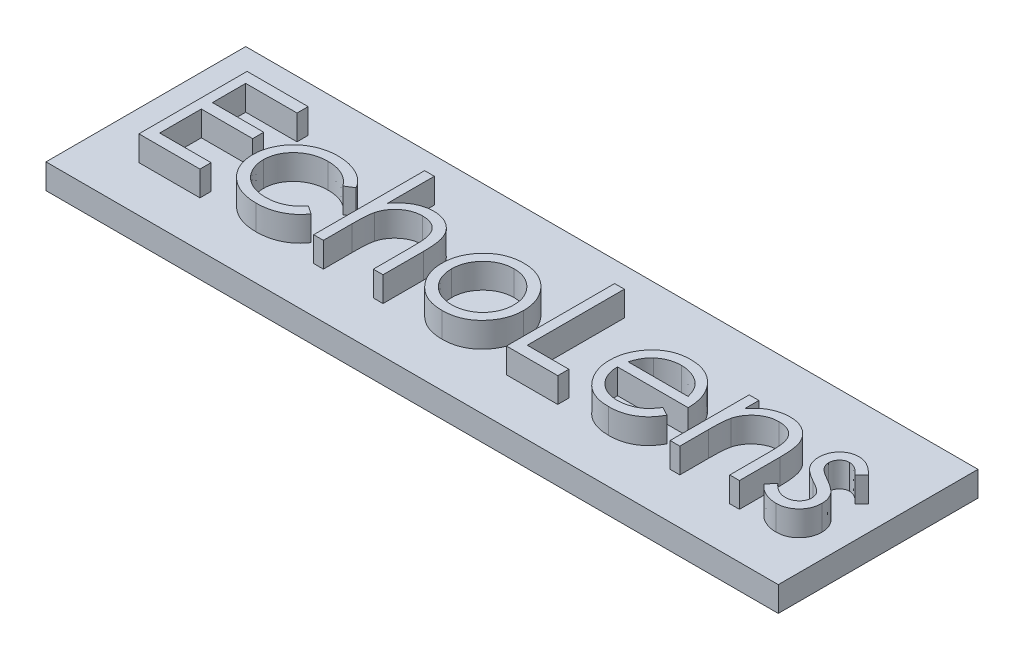
SolidWorks part; units mm, degrees
ref_plane "Front Plane" through (0, 0, 0) normal (0, 0, 1) x (1, 0, 0)
ref_plane "Top Plane" through (0, 0, 0) normal (0, 1, 0) x (1, 0, 0)
ref_plane "Right Plane" through (0, 0, 0) normal (1, 0, 0) x (0, 0, -1)
sketch "Sketch1" plane through (0, 0, 0) normal (0, 1, 0) x (1, 0, 0)
  line L0 (-20, 0) -> (20, 0) construction
  line L1 (-19.1667, 6.5) -> (-15.5, 6.5)
  line L2 (-15.5, 6.5) -> (-15.5, 5.8333)
  line L3 (-15.5, 5.8333) -> (-18.5833, 5.8333)
  line L4 (-18.5833, 5.8333) -> (-18.5833, 3.8333)
  line L5 (-18.5833, 3.8333) -> (-15.5, 3.8333)
  line L6 (-15.5, 3.8333) -> (-15.5, 3.1667)
  line L7 (-15.5, 3.1667) -> (-18.5833, 3.1667)
  line L8 (-18.5833, 3.1667) -> (-18.5833, 0.6667)
  line L9 (-18.5833, 0.6667) -> (-15.5, 0.6667)
  line L10 (-15.5, 0.6667) -> (-15.5, 0)
  line L11 (-15.5, 0) -> (-19.1667, 0)
  line L12 (-19.1667, 0) -> (-19.1667, 6.5)
  line L13 (-9.8333, 3.7201) -> (-10.3216, 3.4167)
  line L14 (-10.3216, 1.3333) -> (-9.8333, 1.013)
  line L15 (-8.6667, 6.6667) -> (-8.0833, 6.6667)
  line L16 (-8.0833, 6.6667) -> (-8.0833, 3.8529)
  line L17 (-4.5, 2.4258) -> (-4.5, 0)
  line L18 (-4.5, 0) -> (-5.0833, 0)
  line L19 (-5.0833, 0) -> (-5.0833, 2.2344)
  line L20 (-8.0833, 1.7174) -> (-8.0833, 0)
  line L21 (-8.0833, 0) -> (-8.6667, 0)
  line L22 (-8.6667, 0) -> (-8.6667, 6.6667)
  line L23 (2.9167, 6.5) -> (3.5, 6.5)
  line L24 (3.5, 6.5) -> (3.5, 0.6667)
  line L25 (3.5, 0.6667) -> (6, 0.6667)
  line L26 (6, 0.6667) -> (6, 0)
  line L27 (6, 0) -> (2.9167, 0)
  line L28 (2.9167, 0) -> (2.9167, 6.5)
  line L29 (10.8151, 1.5) -> (11.3333, 1.2279)
  line L30 (11.5833, 2.25) -> (7.3333, 2.25)
  line L31 (7.3945, 2.8333) -> (11, 2.8333)
  line L32 (12.75, 4.75) -> (13.3333, 4.75)
  line L33 (13.3333, 4.75) -> (13.3333, 3.8932)
  line L34 (16.9167, 2.4258) -> (16.9167, 0)
  line L35 (16.9167, 0) -> (16.3333, 0)
  line L36 (16.3333, 0) -> (16.3333, 2.2344)
  line L37 (13.3333, 1.7174) -> (13.3333, 0)
  line L38 (13.3333, 0) -> (12.75, 0)
  line L39 (12.75, 0) -> (12.75, 4.75)
  line L40 (20.5, 4.1576) -> (20.1042, 3.75)
  line L41 (17.8333, 0.5599) -> (18.2201, 1)
  line L43 (-22, 9.25) -> (22, 9.25)
  line L44 (-22, 9.25) -> (-22, -2.75)
  line L45 (-22, -2.75) -> (22, -2.75)
  line L46 (22, 9.25) -> (22, -2.75)
  spline S0 degree 3 poles (-10.3216, 3.4167) (-10.4224, 3.5511) (-10.5946, 3.7325) (-10.8586, 3.9283) (-11.0689, 4.0467) (-11.2944, 4.138) (-11.6201, 4.2264) (-11.877, 4.2503) (-12.0508, 4.25) knots 0 0 0 0 0.252584 0.373506 0.493364 0.614609 0.73847 1 1 1 1
  spline S1 degree 3 poles (-12.0508, 4.25) (-12.1908, 4.248) (-12.3987, 4.2357) (-12.6645, 4.1761) (-12.8521, 4.1183) (-13.0299, 4.0407) (-13.1982, 3.9464) (-13.3587, 3.8367) (-13.5065, 3.7096) (-13.6418, 3.5715) (-13.759, 3.4234) (-13.861, 3.2697) (-13.9411, 3.1068) (-14.0065, 2.9382) (-14.065, 2.699) (-14.084, 2.5135) (-14.0833, 2.388) knots 0 0 0 0 0.136921 0.201969 0.265462 0.328248 0.390817 0.45355 0.517542 0.580738 0.641922 0.701597 0.760313 0.818757 0.877718 1 1 1 1
  spline S2 degree 3 poles (-14.0833, 2.388) (-14.0829, 2.223) (-14.0506, 1.9744) (-13.9377, 1.6602) (-13.8226, 1.4342) (-13.6768, 1.2251) (-13.5056, 1.0376) (-13.3089, 0.8753) (-13.0884, 0.7406) (-12.8493, 0.6325) (-12.504, 0.5277) (-12.2309, 0.5007) (-12.0469, 0.5) knots 0 0 0 0 0.159965 0.240321 0.322529 0.405024 0.486597 0.567865 0.651333 0.736238 0.821529 1 1 1 1
  spline S3 degree 3 poles (-12.0469, 0.5) (-11.8779, 0.5001) (-11.6274, 0.5237) (-11.3088, 0.6127) (-11.0852, 0.7038) (-10.874, 0.8219) (-10.6058, 1.0188) (-10.4279, 1.1994) (-10.3216, 1.3333) knots 0 0 0 0 0.255447 0.377298 0.498442 0.619372 0.741857 1 1 1 1
  spline S4 degree 3 poles (-9.8333, 1.013) (-9.8897, 0.9272) (-9.9815, 0.8035) (-10.121, 0.6539) (-10.2323, 0.5497) (-10.3495, 0.4508) (-10.4764, 0.3619) (-10.6089, 0.2781) (-10.7487, 0.2027) (-10.8942, 0.1349) (-11.0453, 0.0766) (-11.2012, 0.0265) (-11.3623, -0.0133) (-11.5287, -0.0451) (-11.76, -0.0738) (-11.9367, -0.0852) (-12.056, -0.0833) knots 0 0 0 0 0.119069 0.178197 0.236957 0.295932 0.355856 0.416473 0.477742 0.539903 0.602538 0.665422 0.729765 0.794829 0.861827 1 1 1 1
  spline S5 degree 3 poles (-12.056, -0.0833) (-12.2366, -0.0852) (-12.5029, -0.0624) (-12.8456, 0.0111) (-13.0864, 0.0882) (-13.3154, 0.1876) (-13.5325, 0.3089) (-13.7368, 0.4533) (-13.9265, 0.6182) (-14.1006, 0.7969) (-14.2502, 0.9898) (-14.3799, 1.1897) (-14.4841, 1.4011) (-14.5669, 1.6211) (-14.6438, 1.9318) (-14.6672, 2.173) (-14.6667, 2.3359) knots 0 0 0 0 0.136335 0.201096 0.26445 0.327005 0.389391 0.451976 0.51567 0.578973 0.640167 0.69974 0.758685 0.81782 0.876984 1 1 1 1
  spline S6 degree 3 poles (-14.6667, 2.3359) (-14.6683, 2.4476) (-14.654, 2.6135) (-14.6213, 2.8322) (-14.5805, 2.9912) (-14.5332, 3.1483) (-14.4729, 3.3017) (-14.4022, 3.452) (-14.3219, 3.5989) (-14.2314, 3.7399) (-14.1314, 3.8732) (-14.0254, 4.0003) (-13.9087, 4.1167) (-13.786, 4.2273) (-13.654, 4.329) (-13.5134, 4.4221) (-13.3664, 4.5084) (-13.2129, 4.5852) (-13.054, 4.6514) (-12.8906, 4.7079) (-12.7224, 4.7527) (-12.5506, 4.7902) (-12.3122, 4.8223) (-12.1306, 4.834) (-12.0078, 4.8333) knots 0 0 0 0 0.082136 0.122636 0.162831 0.203007 0.243526 0.284173 0.32541 0.366855 0.407551 0.448187 0.488683 0.529015 0.569843 0.61137 0.653238 0.695446 0.737751 0.780043 0.822807 0.865978 0.909595 1 1 1 1
  spline S7 degree 3 poles (-12.0078, 4.8333) (-11.8526, 4.8338) (-11.6211, 4.8144) (-11.3179, 4.7561) (-11.0985, 4.6919) (-10.8891, 4.6142) (-10.6931, 4.5269) (-10.5151, 4.4255) (-10.3518, 4.3146) (-10.203, 4.1894) (-10.019, 3.9996) (-9.9014, 3.8368) (-9.8333, 3.7201) knots 0 0 0 0 0.182081 0.27191 0.362049 0.450066 0.533976 0.613602 0.690198 0.765413 0.841437 1 1 1 1
  spline S8 degree 3 poles (-8.0833, 3.8529) (-7.966, 4.0089) (-7.7716, 4.2191) (-7.4828, 4.4546) (-7.2593, 4.5919) (-7.0271, 4.7002) (-6.7025, 4.8039) (-6.4468, 4.833) (-6.276, 4.8333) knots 0 0 0 0 0.273996 0.400684 0.522555 0.641534 0.759969 1 1 1 1
  spline S9 degree 3 poles (-6.276, 4.8333) (-6.1045, 4.8322) (-5.8484, 4.8043) (-5.5317, 4.6878) (-5.315, 4.5706) (-5.1203, 4.4244) (-4.9479, 4.2558) (-4.8071, 4.0602) (-4.7112, 3.8796) (-4.6489, 3.7189) (-4.6094, 3.581) (-4.576, 3.4274) (-4.5468, 3.2581) (-4.5274, 3.0723) (-4.5056, 2.7934) (-4.4986, 2.5761) (-4.5, 2.4258) knots 0 0 0 0 0.151155 0.223454 0.295497 0.36692 0.436794 0.506696 0.577864 0.615912 0.658048 0.703776 0.75408 0.808979 0.867913 1 1 1 1
  spline S10 degree 3 poles (-5.0833, 2.2344) (-5.0842, 2.3581) (-5.0846, 2.5352) (-5.0916, 2.7605) (-5.0996, 2.9041) (-5.1082, 3.031) (-5.1224, 3.1665) (-5.1379, 3.2593) (-5.151, 3.3151) knots 0 0 0 0 0.342141 0.489871 0.623312 0.740056 0.841468 1 1 1 1
  spline S11 degree 3 poles (-5.151, 3.3151) (-5.1871, 3.4575) (-5.2624, 3.6607) (-5.4263, 3.8872) (-5.5708, 4.0208) (-5.739, 4.1255) (-6.0064, 4.2265) (-6.2273, 4.2507) (-6.3789, 4.25) knots 0 0 0 0 0.261954 0.379638 0.494379 0.609866 0.729887 1 1 1 1
  spline S12 degree 3 poles (-6.3789, 4.25) (-6.4717, 4.2504) (-6.6105, 4.2399) (-6.79, 4.2011) (-6.9207, 4.1623) (-7.0459, 4.1095) (-7.1691, 4.0483) (-7.2868, 3.9735) (-7.4012, 3.8895) (-7.5076, 3.7965) (-7.6066, 3.6983) (-7.6949, 3.5938) (-7.7749, 3.4846) (-7.8439, 3.3692) (-7.9247, 3.2082) (-7.9701, 3.08) (-7.9935, 2.9922) knots 0 0 0 0 0.126694 0.189084 0.250363 0.312516 0.374243 0.43785 0.502657 0.567745 0.630576 0.692772 0.754268 0.815121 0.876051 1 1 1 1
  spline S13 degree 3 poles (-7.9935, 2.9922) (-8.0109, 2.9236) (-8.0304, 2.8103) (-8.0495, 2.6461) (-8.0626, 2.4958) (-8.0707, 2.3269) (-8.0827, 2.0657) (-8.0825, 1.8602) (-8.0833, 1.7174) knots 0 0 0 0 0.165611 0.269045 0.387448 0.518827 0.665394 1 1 1 1
  spline S14 degree 3 poles (-0.8724, 4.8333) (-0.6977, 4.8351) (-0.4391, 4.8099) (-0.1083, 4.727) (0.1253, 4.6431) (0.3452, 4.5303) (0.6281, 4.3491) (0.8169, 4.1769) (0.9323, 4.0508) knots 0 0 0 0 0.258332 0.382134 0.503804 0.624693 0.746871 1 1 1 1
  spline S15 degree 3 poles (0.9323, 4.0508) (1.0382, 3.935) (1.1801, 3.7494) (1.3328, 3.4813) (1.424, 3.2729) (1.4958, 3.0568) (1.5648, 2.7542) (1.5825, 2.5197) (1.5833, 2.362) knots 0 0 0 0 0.253834 0.376506 0.498534 0.621368 0.744565 1 1 1 1
  spline S16 degree 3 poles (1.5833, 2.362) (1.5843, 2.2031) (1.5625, 1.967) (1.4908, 1.6617) (1.415, 1.4428) (1.3178, 1.2313) (1.1991, 1.0281) (1.0582, 0.8328) (0.8985, 0.6471) (0.722, 0.476) (0.5305, 0.3268) (0.3278, 0.199) (0.1111, 0.096) (-0.1174, 0.0149) (-0.4444, -0.0628) (-0.6998, -0.0827) (-0.8724, -0.0833) knots 0 0 0 0 0.123337 0.183265 0.243172 0.302898 0.363774 0.425605 0.489659 0.553785 0.616222 0.677854 0.739517 0.802097 0.865866 1 1 1 1
  spline S17 degree 3 poles (-0.8724, -0.0833) (-1.0459, -0.0825) (-1.3022, -0.0631) (-1.63, 0.0149) (-1.8589, 0.0963) (-2.0764, 0.199) (-2.2803, 0.3264) (-2.472, 0.476) (-2.6485, 0.6471) (-2.8082, 0.8328) (-2.9491, 1.0281) (-3.0678, 1.2313) (-3.165, 1.4428) (-3.2408, 1.6617) (-3.3125, 1.967) (-3.3343, 2.2031) (-3.3333, 2.362) knots 0 0 0 0 0.134635 0.198324 0.260825 0.322714 0.384555 0.446913 0.510958 0.574931 0.636685 0.697483 0.757134 0.816966 0.876818 1 1 1 1
  spline S18 degree 3 poles (-3.3333, 2.362) (-3.3324, 2.5193) (-3.3147, 2.7533) (-3.2459, 3.0551) (-3.1741, 3.2704) (-3.0821, 3.4779) (-2.9314, 3.7467) (-2.7871, 3.9308) (-2.6823, 4.0469) knots 0 0 0 0 0.255238 0.378679 0.501088 0.622714 0.746241 1 1 1 1
  spline S19 degree 3 poles (-2.6823, 4.0469) (-2.5679, 4.1747) (-2.3775, 4.3453) (-2.0952, 4.5301) (-1.8729, 4.6407) (-1.6395, 4.7275) (-1.3073, 4.8099) (-1.048, 4.8349) (-0.8724, 4.8333) knots 0 0 0 0 0.252713 0.374819 0.496436 0.617911 0.741288 1 1 1 1
  spline S20 degree 3 poles (-0.875, 4.25) (-0.9994, 4.2497) (-1.1843, 4.2329) (-1.4219, 4.1751) (-1.5917, 4.1146) (-1.7545, 4.0364) (-1.9103, 3.9404) (-2.0597, 3.8278) (-2.1997, 3.6988) (-2.3282, 3.5579) (-2.4405, 3.4077) (-2.536, 3.2508) (-2.6156, 3.0869) (-2.6748, 2.9144) (-2.7331, 2.6726) (-2.7497, 2.4846) (-2.75, 2.3581) knots 0 0 0 0 0.126044 0.187165 0.247399 0.30838 0.36978 0.432584 0.497641 0.562401 0.625557 0.687332 0.748313 0.809791 0.871768 1 1 1 1
  spline S21 degree 3 poles (-2.75, 2.3581) (-2.7496, 2.1934) (-2.7206, 1.9458) (-2.6123, 1.6338) (-2.5036, 1.4117) (-2.3672, 1.2062) (-2.2066, 1.0229) (-2.0234, 0.8647) (-1.8198, 0.7334) (-1.6, 0.6293) (-1.2873, 0.5292) (-1.0409, 0.4981) (-0.875, 0.5) knots 0 0 0 0 0.168179 0.251488 0.335841 0.419834 0.502345 0.583649 0.665931 0.748717 0.831047 1 1 1 1
  spline S22 degree 3 poles (-0.875, 0.5) (-0.7092, 0.4983) (-0.463, 0.5287) (-0.1509, 0.6296) (0.0686, 0.7333) (0.2721, 0.8652) (0.4566, 1.022) (0.6159, 1.2067) (0.7521, 1.412) (0.8625, 1.6335) (0.9704, 1.9459) (0.9997, 2.1933) (1, 2.3581) knots 0 0 0 0 0.168983 0.250908 0.333708 0.416005 0.49766 0.579893 0.663902 0.748466 0.831791 1 1 1 1
  spline S23 degree 3 poles (1, 2.3581) (0.9997, 2.4846) (0.9831, 2.6726) (0.9248, 2.9144) (0.8655, 3.0868) (0.7862, 3.2512) (0.6889, 3.4073) (0.577, 3.5584) (0.447, 3.6983) (0.3072, 3.8278) (0.1577, 3.9404) (0.0021, 4.036) (-0.1602, 4.1153) (-0.33, 4.1746) (-0.5669, 4.2333) (-0.7511, 4.2493) (-0.875, 4.25) knots 0 0 0 0 0.128274 0.19027 0.251768 0.312769 0.374793 0.43797 0.503047 0.568125 0.63095 0.692369 0.752973 0.813641 0.874355 1 1 1 1
  spline S24 degree 3 poles (11.3333, 1.2279) (11.2563, 1.0836) (11.1272, 0.8812) (10.9286, 0.6402) (10.7706, 0.4884) (10.6041, 0.356) (10.4282, 0.2403) (10.2419, 0.1416) (10.0453, 0.0585) (9.8368, -0.0053) (9.5352, -0.0672) (9.2996, -0.0833) (9.1393, -0.0833) knots 0 0 0 0 0.181661 0.265874 0.346355 0.4246 0.501903 0.579992 0.658443 0.738672 0.821894 1 1 1 1
  spline S25 degree 3 poles (9.1393, -0.0833) (8.9615, -0.0833) (8.6998, -0.0628) (8.3669, 0.0173) (8.1381, 0.0989) (7.925, 0.2055) (7.7272, 0.3355) (7.5437, 0.488) (7.3802, 0.6644) (7.233, 0.8533) (7.1032, 1.0501) (6.9946, 1.2543) (6.9063, 1.4646) (6.835, 1.6798) (6.768, 1.9778) (6.7517, 2.2078) (6.75, 2.362) knots 0 0 0 0 0.139629 0.204797 0.268135 0.329814 0.391301 0.453434 0.516552 0.579631 0.641119 0.701294 0.76081 0.819932 0.87892 1 1 1 1
  spline S26 degree 3 poles (6.75, 2.362) (6.7518, 2.5065) (6.7653, 2.7221) (6.824, 3.0017) (6.8837, 3.2039) (6.9609, 3.3999) (7.0875, 3.6553) (7.2086, 3.8337) (7.2969, 3.9479) knots 0 0 0 0 0.253768 0.377428 0.500551 0.623296 0.746578 1 1 1 1
  spline S27 degree 3 poles (7.2969, 3.9479) (7.4094, 4.0885) (7.5928, 4.2852) (7.88, 4.4909) (8.1058, 4.6172) (8.3479, 4.7131) (8.6943, 4.8106) (8.9689, 4.8311) (9.1536, 4.8333) knots 0 0 0 0 0.253589 0.374643 0.49534 0.616325 0.739759 1 1 1 1
  spline S28 degree 3 poles (9.1536, 4.8333) (9.3446, 4.8341) (9.6267, 4.8065) (9.9844, 4.7075) (10.233, 4.6052) (10.4664, 4.473) (10.7603, 4.2519) (10.9524, 4.0482) (11.0664, 3.8984) knots 0 0 0 0 0.259033 0.38188 0.502258 0.622752 0.744743 1 1 1 1
  spline S29 degree 3 poles (11.0664, 3.8984) (11.1516, 3.7891) (11.2629, 3.6115) (11.381, 3.3574) (11.4523, 3.1552) (11.5099, 2.9438) (11.5667, 2.6423) (11.5804, 2.4083) (11.5833, 2.25) knots 0 0 0 0 0.236255 0.356174 0.47725 0.60154 0.729618 1 1 1 1
  spline S30 degree 3 poles (7.3333, 2.25) (7.3367, 2.127) (7.3531, 1.9452) (7.4094, 1.7127) (7.4674, 1.551) (7.5377, 1.397) (7.6239, 1.2518) (7.7267, 1.1162) (7.8413, 0.9888) (7.9689, 0.8754) (8.1031, 0.7739) (8.2459, 0.6889) (8.3962, 0.6198) (8.5536, 0.5658) (8.7764, 0.5155) (8.9494, 0.4994) (9.0664, 0.5) knots 0 0 0 0 0.134476 0.198391 0.260753 0.321829 0.383037 0.444653 0.507398 0.569825 0.630778 0.690929 0.750945 0.811049 0.872331 1 1 1 1
  spline S31 degree 3 poles (9.0664, 0.5) (9.1819, 0.4994) (9.3552, 0.513) (9.5815, 0.5604) (9.7472, 0.6085) (9.9062, 0.6671) (10.0533, 0.7379) (10.1887, 0.8162) (10.3152, 0.9057) (10.4378, 1.0153) (10.6115, 1.21) (10.7361, 1.3764) (10.8151, 1.5) knots 0 0 0 0 0.163879 0.245659 0.327726 0.40861 0.485749 0.559169 0.630268 0.705306 0.792065 1 1 1 1
  spline S32 degree 3 poles (11, 2.8333) (10.9631, 2.9833) (10.8895, 3.1948) (10.7549, 3.4491) (10.6406, 3.6081) (10.5109, 3.7492) (10.3611, 3.8726) (10.1932, 3.9829) (10.0079, 4.0761) (9.8117, 4.1552) (9.5372, 4.2269) (9.3256, 4.2521) (9.1836, 4.25) knots 0 0 0 0 0.185231 0.267501 0.3444 0.419595 0.496891 0.576638 0.660268 0.745387 0.83004 1 1 1 1
  spline S33 degree 3 poles (9.1836, 4.25) (9.0686, 4.2503) (8.8977, 4.2378) (8.6779, 4.1901) (8.5206, 4.1419) (8.3709, 4.0776) (8.1758, 3.9765) (8.0442, 3.8758) (7.9596, 3.8047) knots 0 0 0 0 0.259141 0.384162 0.505992 0.629098 0.750669 1 1 1 1
  spline S34 degree 3 poles (7.9596, 3.8047) (7.8949, 3.7501) (7.8072, 3.6556) (7.7018, 3.5167) (7.6287, 3.3997) (7.5618, 3.2723) (7.4759, 3.0854) (7.4251, 2.9361) (7.3945, 2.8333) knots 0 0 0 0 0.22258 0.3385 0.458709 0.585535 0.717518 1 1 1 1
  spline S35 degree 3 poles (13.3333, 3.8932) (13.451, 4.0459) (13.6384, 4.2593) (13.9305, 4.4832) (14.1533, 4.6135) (14.3867, 4.7115) (14.7126, 4.8073) (14.9689, 4.8324) (15.1406, 4.8333) knots 0 0 0 0 0.273569 0.398988 0.51993 0.63811 0.756589 1 1 1 1
  spline S36 degree 3 poles (15.1406, 4.8333) (15.3122, 4.8322) (15.5682, 4.8043) (15.885, 4.6878) (16.1016, 4.5705) (16.2968, 4.4245) (16.4683, 4.2544) (16.6101, 4.0588) (16.7052, 3.8773) (16.7678, 3.7163) (16.8072, 3.5784) (16.8407, 3.4248) (16.8698, 3.2559) (16.8894, 3.0706) (16.911, 2.7925) (16.9181, 2.5756) (16.9167, 2.4258) knots 0 0 0 0 0.151178 0.223488 0.295543 0.366976 0.437131 0.507044 0.57856 0.616614 0.658756 0.704491 0.754803 0.809332 0.868274 1 1 1 1
  spline S37 degree 3 poles (16.3333, 2.2344) (16.3324, 2.3581) (16.3322, 2.5352) (16.3249, 2.7605) (16.3176, 2.9042) (16.3068, 3.0309) (16.2932, 3.1665) (16.2774, 3.2593) (16.2643, 3.3151) knots 0 0 0 0 0.34211 0.489826 0.623254 0.74008 0.841483 1 1 1 1
  spline S38 degree 3 poles (16.2643, 3.3151) (16.2318, 3.4577) (16.1581, 3.6613) (15.9942, 3.8871) (15.8496, 4.0212) (15.6802, 4.1254) (15.4119, 4.2261) (15.1907, 4.2509) (15.0391, 4.25) knots 0 0 0 0 0.260833 0.378476 0.493178 0.609281 0.729981 1 1 1 1
  spline S39 degree 3 poles (15.0391, 4.25) (14.9463, 4.2504) (14.8075, 4.2399) (14.628, 4.2011) (14.4972, 4.1624) (14.3718, 4.1091) (14.2478, 4.0487) (14.1299, 3.9734) (14.0155, 3.8895) (13.9091, 3.7965) (13.81, 3.6983) (13.7217, 3.5938) (13.6417, 3.4846) (13.5727, 3.3692) (13.4919, 3.2082) (13.4466, 3.08) (13.4232, 2.9922) knots 0 0 0 0 0.126627 0.188984 0.25023 0.312351 0.374574 0.438148 0.50292 0.567974 0.630771 0.692935 0.754398 0.815218 0.876117 1 1 1 1
  spline S40 degree 3 poles (13.4232, 2.9922) (13.4058, 2.9227) (13.3864, 2.8086) (13.3672, 2.6435) (13.354, 2.4932) (13.3461, 2.3247) (13.3339, 2.0644) (13.3342, 1.8598) (13.3333, 1.7174) knots 0 0 0 0 0.167615 0.271052 0.38946 0.520843 0.666399 1 1 1 1
  spline S41 degree 3 poles (20.1042, 3.75) (20.0395, 3.8271) (19.9402, 3.9347) (19.7957, 4.0536) (19.6935, 4.126) (19.5905, 4.1806) (19.4566, 4.233) (19.3522, 4.2499) (19.2839, 4.25) knots 0 0 0 0 0.305036 0.441309 0.565963 0.683525 0.793334 1 1 1 1
  spline S42 degree 3 poles (19.2839, 4.25) (19.2028, 4.2517) (19.0819, 4.2255) (18.9383, 4.1446) (18.8451, 4.0593) (18.7663, 3.9613) (18.6889, 3.8149) (18.6669, 3.6923) (18.6667, 3.6107) knots 0 0 0 0 0.245901 0.369166 0.498511 0.628504 0.751028 1 1 1 1
  spline S43 degree 3 poles (18.6667, 3.6107) (18.6668, 3.5357) (18.6959, 3.3794) (18.7786, 3.2438) (18.8281, 3.1797) knots 0 0 0 0 0.479403 1 1 1 1
  spline S44 degree 3 poles (18.8281, 3.1797) (18.8578, 3.1394) (18.9158, 3.0845) (19.0004, 3.0099) (19.0808, 2.9505) (19.1714, 2.8881) (19.3141, 2.8) (19.4259, 2.7321) (19.5065, 2.6901) knots 0 0 0 0 0.17756 0.283982 0.402217 0.533568 0.676121 1 1 1 1
  spline S45 degree 3 poles (19.5065, 2.6901) (19.6044, 2.636) (19.7453, 2.5545) (19.9193, 2.4378) (20.0334, 2.3549) (20.1336, 2.271) (20.2481, 2.1666) (20.3208, 2.0816) (20.362, 2.0234) knots 0 0 0 0 0.307115 0.446213 0.574876 0.694152 0.804581 1 1 1 1
  spline S46 degree 3 poles (20.362, 2.0234) (20.4327, 1.9166) (20.5517, 1.6814) (20.5815, 1.4195) (20.5833, 1.2891) knots 0 0 0 0 0.495235 1 1 1 1
  spline S47 degree 3 poles (20.5833, 1.2891) (20.5825, 1.1967) (20.5722, 1.0591) (20.5295, 0.8832) (20.4867, 0.7575) (20.4288, 0.6387) (20.3609, 0.5239) (20.2794, 0.4155) (20.1864, 0.3136) (20.0845, 0.2206) (19.9759, 0.1388) (19.8603, 0.0709) (19.7386, 0.0147) (19.6105, -0.03) (19.4285, -0.072) (19.2868, -0.0827) (19.1914, -0.0833) knots 0 0 0 0 0.127199 0.188597 0.24864 0.309525 0.370037 0.431889 0.495704 0.559519 0.621372 0.682397 0.743568 0.805498 0.86864 1 1 1 1
  spline S48 degree 3 poles (19.1914, -0.0833) (19.0609, -0.0843) (18.8656, -0.0618) (18.6138, 0.0101) (18.4311, 0.0837) (18.2583, 0.177) (18.048, 0.3248) (17.9118, 0.4604) (17.8333, 0.5599) knots 0 0 0 0 0.251724 0.377219 0.504694 0.631458 0.755401 1 1 1 1
  spline S49 degree 3 poles (18.2201, 1) (18.29, 0.9222) (18.3982, 0.8132) (18.5577, 0.6953) (18.6743, 0.6235) (18.7936, 0.5683) (18.9542, 0.5164) (19.0789, 0.4996) (19.1615, 0.5) knots 0 0 0 0 0.285904 0.417172 0.540501 0.659238 0.775006 1 1 1 1
  spline S50 degree 3 poles (19.1615, 0.5) (19.2714, 0.499) (19.4345, 0.5274) (19.6308, 0.6236) (19.7572, 0.7239) (19.8646, 0.8409) (19.9688, 1.016) (20.0006, 1.1655) (20, 1.2643) knots 0 0 0 0 0.261896 0.387836 0.517686 0.644509 0.764718 1 1 1 1
  spline S51 degree 3 poles (20, 1.2643) (19.9997, 1.346) (19.9737, 1.5099) (19.8916, 1.6544) (19.8398, 1.7174) knots 0 0 0 0 0.500453 1 1 1 1
  spline S52 degree 3 poles (19.8398, 1.7174) (19.8086, 1.7551) (19.7506, 1.8097) (19.6616, 1.8804) (19.5779, 1.9405) (19.4813, 2.0029) (19.3278, 2.0932) (19.2059, 2.1616) (19.1198, 2.207) knots 0 0 0 0 0.167462 0.27227 0.389551 0.520801 0.666263 1 1 1 1
  spline S53 degree 3 poles (19.1198, 2.207) (19.0258, 2.259) (18.8903, 2.3364) (18.7249, 2.4509) (18.6151, 2.5306) (18.5183, 2.6113) (18.4107, 2.716) (18.3397, 2.7978) (18.3008, 2.8555) knots 0 0 0 0 0.30595 0.443775 0.572824 0.692154 0.802296 1 1 1 1
  spline S54 degree 3 poles (18.3008, 2.8555) (18.2279, 2.9602) (18.1194, 3.1977) (18.081, 3.4559) (18.0833, 3.5872) knots 0 0 0 0 0.492591 1 1 1 1
  spline S55 degree 3 poles (18.0833, 3.5872) (18.0839, 3.6729) (18.0916, 3.8004) (18.13, 3.963) (18.1654, 4.0784) (18.2145, 4.1871) (18.2733, 4.2904) (18.3424, 4.3884) (18.4219, 4.4794) (18.5094, 4.562) (18.6039, 4.6341) (18.7034, 4.6956) (18.8081, 4.7471) (18.9192, 4.7861) (19.0774, 4.8228) (19.2004, 4.8343) (19.2839, 4.8333) knots 0 0 0 0 0.133044 0.196507 0.258613 0.319728 0.380873 0.442636 0.505079 0.567881 0.628814 0.68891 0.748765 0.809386 0.870884 1 1 1 1
  spline S56 degree 3 poles (19.2839, 4.8333) (19.3858, 4.8332) (19.5416, 4.8115) (19.742, 4.7401) (19.8949, 4.6655) (20.0468, 4.5687) (20.2575, 4.4074) (20.406, 4.264) (20.5, 4.1576) knots 0 0 0 0 0.213412 0.326127 0.444452 0.569061 0.702712 1 1 1 1
  point P4 (0, 0)
  point P656 (0, -2.75)
  dimension "D1" = 40
  dimension "D2" = 44
  dimension "D3" = 12
  dimension "D4" = 2.75
extrude "Boss-Extrude1" add sketch "Sketch1" against normal blind 1.5 contours L46 L43 L44 L45 L11 L12 L1 L2 L3 L4 L5 L6 L7 L8 L9 L10 S5 S6 S7 L13 S0 S1 S2 S3 L14 S4 L22 L15 L16 S8 S9 L17 S17 S18 S19 S14 S15 S16 L28 L23 L24 L25 L26 | S48 L0 S47 S46 S45 S44 S43 S42 S41 L40 S56 S55 S54 S53 S52 S51 S50 S49 L41 | S25 L0 S24 L29 S31 S30 L30 S29 S28 S27 S26 S34 S33 S32 L31 | S33 S34 L31 S32 | S17 L0 S16 S15 S14 S19 S18 S23 S22 S21 S20 | S22 S23 S20 S21 | L28 L27 L26 L25 L24 L23 | S40 S39 S38 S37 L36 L35 L34 S36 S35 L33 L32 L39 L38 L37 | L37 L0 L36 S37 S38 S39 S40 | S13 S12 S11 S10 L19 L18 L17 S9 S8 L16 L15 L22 L21 L20 | L20 L0 L19 S10 S11 S12 S13 | S5 L0 S4 L14 S3 S2 S1 S0 L13 S7 S6 | L12 L11 L10 L9 L8 L7 L6 L5 L4 L3 L2 L1 | L0 S5 S4 | L0 S17 S16 | L0 S25 S24 | L0 S48 S47 region at (-17.7397, 0, -3.3016) region at (19.2851, 0, -2.3436) region at (19.181, 0, 0.0336) region at (12.8138, 0, -2.375) region at (9.0407, 0, -2.4483) region at (9.1433, 0, 0.0337) region at (2.9886, 0, -3.25) region at (-2.7873, 0, -0.9242) region at (-0.8736, 0, 0.0335) region at (-8.588, 0, -3.3333) region at (-14.0812, 0, -0.8869) region at (-12.0501, 0, 0.0338) region at (-6.5549, 0, -1.9746) region at (14.862, 0, -1.9749) region at (9.2005, 0, -3.4293) region at (0, 0, -8.7939) region at (-0.8753, 0, -2.3686)
extrude "Boss-Extrude2" add sketch "Sketch1<3>" along normal blind 1.5 contours S48 L0 S47 S46 S45 S44 S43 S42 S41 L40 S56 S55 S54 S53 S52 S51 S50 S49 L41 | L0 S48 S47 | S40 S39 S38 S37 L36 L35 L34 S36 S35 L33 L32 L39 L38 L37 | S25 L0 S24 L29 S31 S30 L30 S29 S28 S27 S26 S34 S33 S32 L31 | L0 S25 S24 | L28 L27 L26 L25 L24 L23 | S17 L0 S16 S15 S14 S19 S18 S23 S22 S21 S20 | L0 S17 S16 | S13 S12 S11 S10 L19 L18 L17 S9 S8 L16 L15 L22 L21 L20 | S5 L0 S4 L14 S3 S2 S1 S0 L13 S7 S6 | L12 L11 L10 L9 L8 L7 L6 L5 L4 L3 L2 L1 | L0 S5 S4 region at (-17.7397, 0, -3.3016) region at (19.2851, 0, -2.3436) region at (19.181, 0, 0.0336) region at (12.8138, 0, -2.375) region at (9.0407, 0, -2.4483) region at (9.1433, 0, 0.0337) region at (2.9886, 0, -3.25) region at (-2.7873, 0, -0.9242) region at (-0.8736, 0, 0.0335) region at (-8.588, 0, -3.3333) region at (-14.0812, 0, -0.8869) region at (-12.0501, 0, 0.0338)
sketch "Sketch1<3>" plane through (0, 0, 0) normal (0, 1, 0) x (1, 0, 0) same geometry as "Sketch1"
